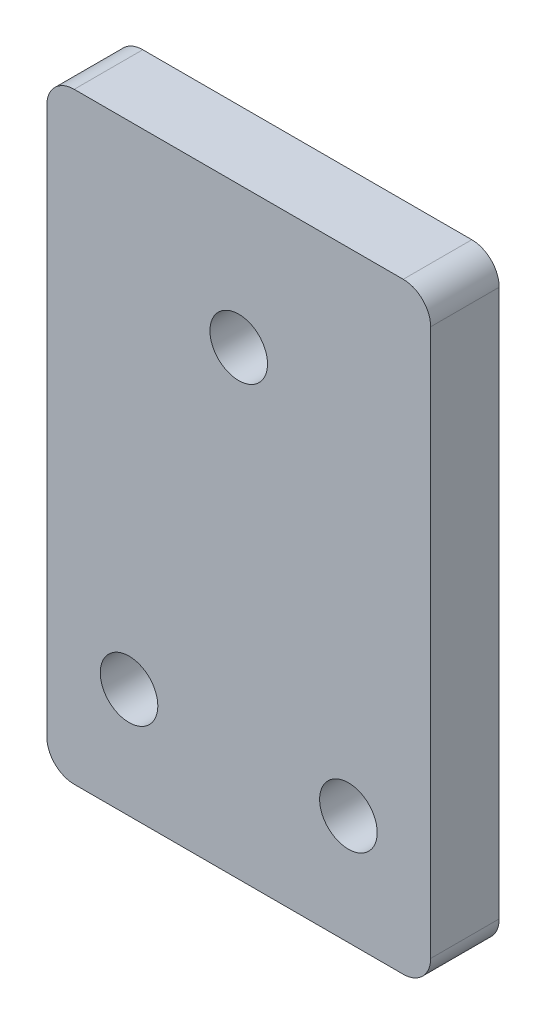
SolidWorks part; units mm, degrees
ref_plane "Front Plane" through (0, 0, 0) normal (0, 0, 1) x (1, 0, 0)
ref_plane "Top Plane" through (0, 0, 0) normal (0, 1, 0) x (1, 0, 0)
ref_plane "Right Plane" through (0, 0, 0) normal (1, 0, 0) x (0, 0, -1)
sketch "Sketch1" plane through (0, 0, 0) normal (0, 0, 1) x (1, 0, 0)
  line L0 (-76.6, 27) -> (-48.4, 27) construction
  line L1 (-76.5, 26.9) -> (-48.5, 26.9)
  line L2 (-76.5, 26.9) -> (-76.5, -17)
  line L3 (-76.5, -17) -> (-48.5, -17)
  line L4 (-48.5, 26.9) -> (-48.5, -17)
  line L5 (-76.6, 2) -> (-76.6, 27) construction
  line L6 (-78.6, 0) -> (-123, 0) construction
  line L7 (-70.5, -9) -> (-54.5, -9) construction
  circle A0 centre (-70.5, -9) radius 2.1
  circle A1 centre (-54.5, -9) radius 2.1
  circle A2 centre (-62.5, 16.6) radius 2.1 construction
  circle A3 centre (-62.5, 16.6) radius 2.1
  point P6 (-62.5, 27)
  point P7 (-62.5, 26.9)
  point P16 (-62.5, -9)
  dimension "D4" = 4.2
  dimension "D1" = 0.1
  dimension "D2" = 0.1
  dimension "D3" = 17
  dimension "D5" = 16
  dimension "D6" = 8
extrude "Boss-Extrude1" add sketch "Sketch1" along normal up to surface (5 mm away)
fillet "Fillet1" radius 2 4 edges at (-48.5, 26.9, 2.5) (-48.5, -17, 2.5) (-76.5, 26.9, 2.5) (-76.5, -17, 2.5)
equation "\"width\"= 24"
equation "\"thk\"= 3"
equation "\"holesize\"= 4.2"
equation "\"holedistance\"= ( 20 + 12 ) / 2"
equation "\"threaded_hole\"= 3.9"
equation "\"fillet_radius\"= 2"
equation "\"ground_clearance\"= 25"
equation "\"tire_thk\"= 3"
equation "\"innerwheel_diam\" = \"wheel_diam\"-2*\"tire_thk\""
equation "\"innerwheel_thk\"= 8"
equation "\"wheel_diam\"= 2*(\"width\"/2+\"ground_clearance\")"
equation "\"coloursensor_holesize\"= 2.65"
equation "\"hole_to_edge\" = 4"
equation "\"D4@Sketch1\"=\"holesize\""
equation "\"D5@Sketch1\"=\"holedistance\""
equation "\"D1@Fillet1\"=\"fillet_radius\""
